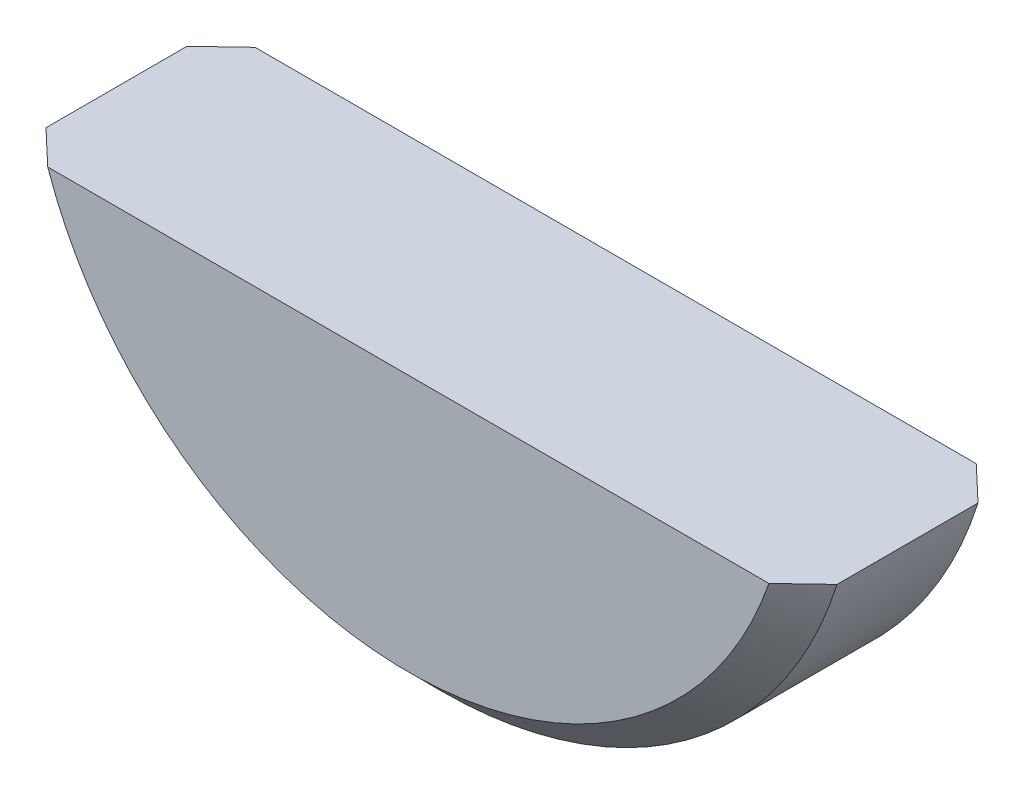
SolidWorks part; units mm, degrees
ref_plane "Front" through (0, 0, 0) normal (0, 0, 1) x (1, 0, 0)
ref_plane "Top" through (0, 0, 0) normal (0, 1, 0) x (1, 0, 0)
ref_plane "Right" through (0, 0, 0) normal (1, 0, 0) x (0, 0, -1)
sketch "Sketch1" plane through (0, 0, 0) normal (0, 0, 1) x (1, 0, 0)
  line L0 (-1.9079, 0) -> (1.9079, 0)
  arc A0 (-1.9079, 0) -> (1.9079, 0) centre (0, 0.6) ccw
  dimension "d0" = 4
  dimension "h" = 1.4
extrude "Extrude1" add sketch "Sketch1" along normal blind 1
sketch "Sketch2" plane through (0, 0, 0) normal (0, 0, 1) x (1, 0, 0)
  line L0 (-1.9079, -1.1) -> (1.9079, -1.1)
  line L1 (1.9079, 0) -> (-1.9079, 0) construction
  dimension "h1" = 1.1
extrude "Cut-Extrude1" [suppressed] cut sketch "Sketch2" against normal through all and the other way through all flip side to cut
chamfer "Chamfer1" distance 0.16 angle 45 2 edges at (0, -1.4, 0) (0, -1.4, 1)
